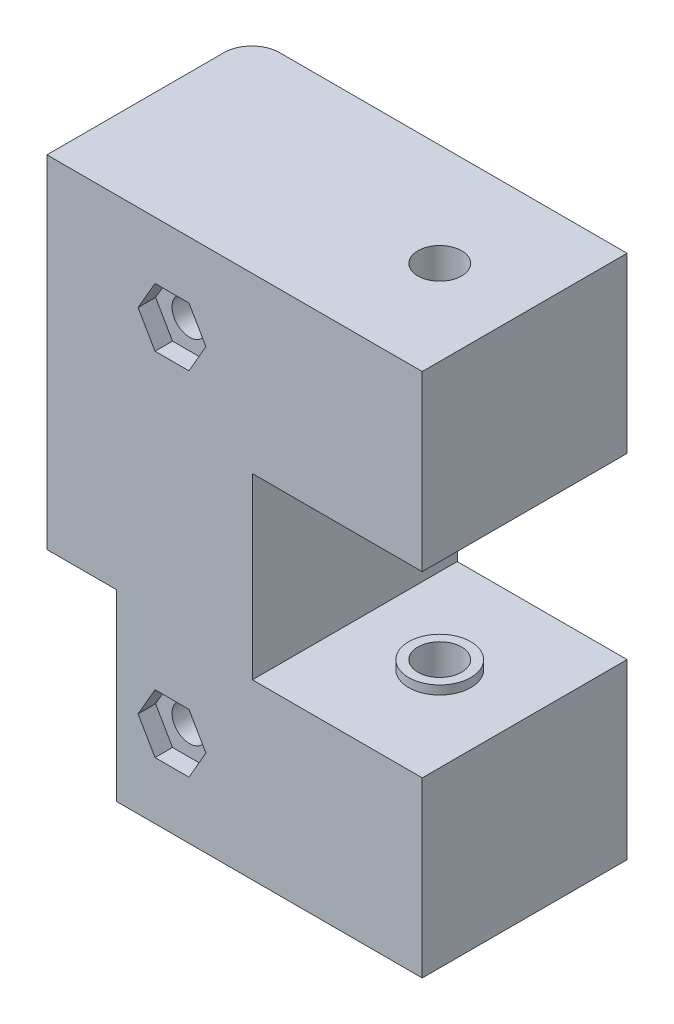
SolidWorks part; units mm, degrees
ref_plane "Front Plane" through (0, 0, 0) normal (0, 0, 1) x (1, 0, 0)
ref_plane "Top Plane" through (0, 0, 0) normal (0, 1, 0) x (1, 0, 0)
ref_plane "Right Plane" through (0, 0, 0) normal (1, 0, 0) x (0, 0, -1)
sketch "MainBlock" plane through (0, 0, 0) normal (0, 0, 1) x (1, 0, 0)
  line L0 (0, 0) -> (42.875, 0)
  line L1 (42.875, 0) -> (42.875, 19.8)
  line L2 (42.875, 19.8) -> (23.475, 19.8)
  line L3 (23.475, 19.8) -> (23.475, 40.2)
  line L4 (23.475, 40.2) -> (42.875, 40.2)
  line L5 (42.875, 40.2) -> (42.875, 60)
  line L6 (42.875, 60) -> (0, 60)
  line L7 (0, 60) -> (0, 0)
  circle A0 centre (14.2875, 50.1) radius 2
  circle A1 centre (14.2875, 9.9) radius 2
  dimension "D4" = 4
  dimension "D1" = 42.875
  dimension "D2" = 60
  dimension "D3" = 20.4
  dimension "D5" = 19.4
  dimension "D6" = 14.2875
  dimension "D7" = 9.9
  dimension "D9" = 19.8
  dimension "D10" = 19.8
  dimension "D8" = 40.2
  dimension "D11" = 9.9
extrude "MainBlockBoss-Extrude1" add sketch "MainBlock" along normal blind 23.4
sketch "TopHoleCut-Sketch2" plane through (0, 60, 0) normal (0, 1, 0) x (1, 0, 0)
  line L0 (42.875, 0) -> (0, 0) construction
  circle A0 centre (33.175, -11.7) radius 2.5
  dimension "D3" = 5
  dimension "D1" = 11.7
  dimension "D2" = 9.7
extrude "TopHoleCut-Extrude1" cut sketch "TopHoleCut-Sketch2" against normal blind 45
sketch "MountHoleBoreSketch3" plane through (0, 0, 23.4) normal (0, 0, 1) x (1, 0, 0)
  line L1 (18.1625, 50.1) -> (16.225, 53.4558)
  line L2 (16.225, 53.4558) -> (12.35, 53.4558)
  line L3 (12.35, 53.4558) -> (10.4125, 50.1)
  line L4 (10.4125, 50.1) -> (12.35, 46.7442)
  line L5 (12.35, 46.7442) -> (16.225, 46.7442)
  line L6 (16.225, 46.7442) -> (18.1625, 50.1)
  line L7 (18.1625, 9.9) -> (16.225, 13.2558)
  line L8 (16.225, 13.2558) -> (12.35, 13.2558)
  line L9 (12.35, 13.2558) -> (10.4125, 9.9)
  line L10 (10.4125, 9.9) -> (12.35, 6.5442)
  line L11 (12.35, 6.5442) -> (16.225, 6.5442)
  line L12 (16.225, 6.5442) -> (18.1625, 9.9)
  circle A0 centre (14.2875, 50.1) radius 3.3558 construction
  circle A1 centre (14.2875, 9.9) radius 3.3558 construction
  point P10 (14.2875, 53.4558)
  dimension "D1" = 7.75
extrude "MountHoleBoreCut-Extrude2" cut sketch "MountHoleBoreSketch3" against normal blind 2
sketch "TopSpacerSketch4" plane through (0, 40.2, 0) normal (0, -1, 0) x (1, 0, 0)
  circle A0 centre (33.175, 11.7) radius 3.55
  circle A1 centre (33.175, 11.7) radius 2.5
  circle A2 centre (33.175, 11.7) radius 2.5 construction
  dimension "D1" = 7.1
extrude "TopSpacerBoss-Extrude2" add sketch "TopSpacerSketch4" along normal blind 1
sketch "LowerSpacerSketch5" plane through (0, 19.8, 0) normal (0, 1, 0) x (1, 0, 0)
  circle A0 centre (33.175, -11.7) radius 2.5
  circle A1 centre (33.175, -11.7) radius 2.5 construction
  circle A2 centre (33.175, -11.7) radius 3.55
  circle A3 centre (33.175, -11.7) radius 3.55 construction
extrude "LowerSpacerBoss-Extrude3" add sketch "LowerSpacerSketch5" along normal blind 1
sketch "PushPinHoleSketch1" plane through (0, 0, 0) normal (0, -1, 0) x (1, 0, 0)
  circle A0 centre (33.175, 11.7) radius 2
  circle A1 centre (33.175, 11.7) radius 2.5 construction
extrude "PushPinHoleCut-Extrude1" cut sketch "PushPinHoleSketch1" against normal through all
sketch "MidRailIndentSketch1" plane through (0, 0, 23.4) normal (0, 0, 1) x (1, 0, 0)
  line L0 (0, 60) -> (0, 0) construction
  line L1 (0, 20.9498) -> (7.9375, 20.9498)
  line L2 (0, 20.9498) -> (0, 0)
  line L3 (0, 0) -> (7.9375, 0)
  line L4 (7.9375, 20.9498) -> (7.9375, 0)
  line L5 (42.875, 60) -> (0, 60) construction
  line L6 (0, 0) -> (42.875, 0) construction
  dimension "D1" = 39.0502
  dimension "D3" = 7.9375
extrude "MidRailIndentCut-Extrude1" cut sketch "MidRailIndentSketch1" against normal through all
fillet "VerticalSupportFillet1" radius 3.175 1 edges at (0, 40.4749, 0)
equation "\"BeltTensionerWidth\"= \"MidRailToAlignWithGantryBlock\" + \"BeltTensionerInnerWidth\" / 2 + \"RailThickness\""
equation "\"BeltTensionerHeight\"= 60mm"
equation "\"BeltTensionerDepth\"= \"BeltTensionerBackWallThickness\" + \"BeltTensionerInnerDepth\"'Equals 23.4"
equation "\"BeltTensionerInnerWidth\"= \"20TGT2PulleyDiameter\" + \"BeltTensionerSpaceBetweenPulleyAndWall\""
equation "\"BeltTensionerInnerHeight\"= \"20TGT2PulleyWidth\" * 2 + \"1mmSpacer\" * 3"
equation "\"BeltTensionerBackWallThickness\"= 4mm"
equation "\"BeltTensionerInnerDepth\"= \"20TGT2PulleyDiameter\" + \"BeltTensionerSpaceBetweenPulleyAndWall\"'Equals 19.4"
equation "\"RailThickness\"= .125in'Spec"
equation "\"HoleOffsetFromEdge\"= \"RailThickness\" * 2.5"
equation "\"MidRailToAlignWithGantryBlock\"= \"Nema17MountStepperHoleDistanceFromBack\"'All outside cogs must align"
equation "\"20TGT2PulleyDiameter\"= 17.9mm'Spec"
equation "\"BeltTensionerSpaceBetweenPulleyAndWall\"= 1.5mm"
equation "\"BeltTensionerMountingHoleDiameter\"= 4.0mm"
equation "\"BeltTensionerMountingHoleOffsetFromTopOrBottom\"= ( \"BeltTensionerHeight\" - \"BeltTensionerInnerHeight\" ) / 4"
equation "\"20TGT2PulleyWidth\"= 8.7mm'The STL of the Pulley in the diagram is a bit larger"
equation "\"1mmSpacer\"= 1mm"
equation "\"SteelShaft5mmHoleDiameter\"= 5mm"
equation "\"BeltTensionerMountingHoleOuterBoreDepth\"= 2mm"
equation "\"BeltTensionerMountingHoleOuterBoreDiameter\"= 7.75mm"
equation "\"7mmx1mmSpacerDiameter\"= 7mm + .1mm'Add .1mm for printing"
equation "\"7mmx1mmSpacerHeight\"= 1mm"
equation "\"D1@MainBlock\" = \"BeltTensionerWidth\""
equation "\"D4@MainBlock\" = \"BeltTensionerMountingHoleDiameter\""
equation "\"D5@MainBlock\" = \"BeltTensionerInnerWidth\""
equation "\"BeltTensionerMountingHoleOffsetFromEdge\"= \"HoleOffsetFromEdge\" + \"RailThickness\" * 2"
equation "\"D6@MainBlock\"=\"BeltTensionerMountingHoleOffsetFromEdge\""
equation "\"D7@MainBlock\"=\"BeltTensionerMountingHoleOffsetFromTopOrBottom\""
equation "\"D1@MainBlockBoss-Extrude1\" = \"BeltTensionerDepth\""
equation "\"D1@TopHoleCut-Sketch2\" = \"BeltTensionerDepth\" / 2"
equation "\"D3@TopHoleCut-Sketch2\" = \"SteelShaft5mmHoleDiameter\""
equation "\"D1@MountHoleBoreSketch3\" = \"BeltTensionerMountingHoleOuterBoreDiameter\""
equation "\"D1@MountHoleBoreCut-Extrude2\"=\"BeltTensionerMountingHoleOuterBoreDepth\""
equation "\"D1@TopSpacerSketch4\" = \"7mmx1mmSpacerDiameter\""
equation "\"D1@TopSpacerBoss-Extrude2\" = \"7mmx1mmSpacerHeight\""
equation "\"D1@LowerSpacerBoss-Extrude3\" = \"7mmx1mmSpacerHeight\""
equation "\"SteelPushPinHoleDiameter\" = \"SteelShaft5mmHoleDiameter\" - 1mm"
equation "\"D1@PushPinHoleSketch1\" = \"SteelPushPinHoleDiameter\""
equation "\"BeltTensionerSteelShaftHoleDepthFromTop\"= ( \"SteelShaftLength\" - \"BeltTensionerInnerHeight\" ) / 2 + ( \"BeltTensionerHeight\" - \"BeltTensionerInnerHeight\" ) / 2 + \"BeltTensionerInnerHeight\"'Equals 45"
equation "\"SteelShaftLength\"= 30mm"
equation "\"D1@TopHoleCut-Extrude1\"=\"BeltTensionerSteelShaftHoleDepthFromTop\""
equation "\"D2@TopHoleCut-Sketch2\"=\"BeltTensionerWidth\" -\"MidRailToAlignWithGantryBlock\" - \"RailThickness\""
equation "\"D1@MidRailIndentSketch1\"=\"DistanceAboveMidSideRailToTopOfBeltTensioner\""
equation "\"DistanceAboveMidSideRailToTopOfBeltTensioner\"= \"VSBeltTensionerY1ToAlignWithYAxisGantryUpperPulleyYSValue\" + \"BeltTensionerMountingHoleOffsetFromTopOrBottom\" - \"V8 ToTopOfMidSideRailYSValue\"'Equals 39.05017"
equation "\"BeltTensionerTopHeight\"= ( \"BeltTensionerHeight\" - \"BeltTensionerInnerHeight\" ) / 2'Equals 19.8"
equation "\"D9@MainBlock\"=\"BeltTensionerTopHeight\""
equation "\"D3@MainBlock\"=\"BeltTensionerInnerHeight\""
equation "\"D2@MainBlock\"=\"BeltTensionerHeight\""
equation "\"V8 ToTopOfMidSideRailYSValue\"= 376.9847mm"
equation "\"D1@VerticalSupportFillet1\"=\"RailThickness\""
equation "\"D3@MidRailIndentSketch1\"=\"HoleOffsetFromEdge\""
equation "\"BeltTensionerDistanceBetweenMountingHoles\"= \"BeltTensionerHeight\" - \"BeltTensionerMountingHoleOffsetFromTopOrBottom\" * 2'Equals 40.2"
equation "\"D8@MainBlock\"=\"BeltTensionerDistanceBetweenMountingHoles\""
equation "\"VSBeltTensionerY1ToAlignWithYAxisGantryUpperPulleyYSValue\"= 406.13487mm"
equation "\"Nema17MountStepperHoleDistanceFromBack\"= 30mm'Spec"
